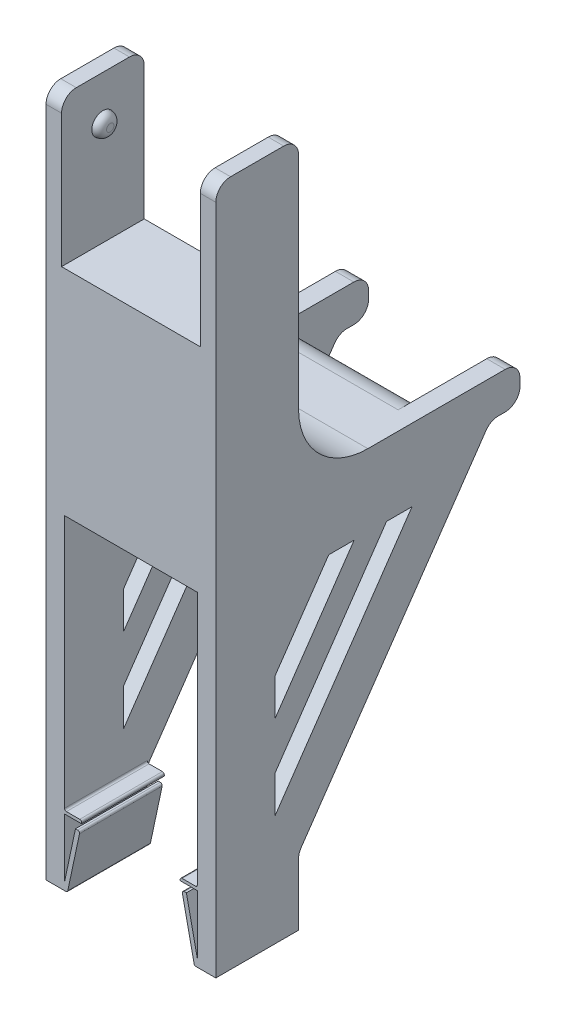
SolidWorks part; units mm, degrees
ref_plane "Front Plane" through (0, 0, 0) normal (0, 0, 1) x (1, 0, 0)
ref_plane "Top Plane" through (0, 0, 0) normal (0, 1, 0) x (1, 0, 0)
ref_plane "Right Plane" through (0, 0, 0) normal (1, 0, 0) x (0, 0, -1)
sketch "Szkic1" plane through (0, 0, 0) normal (1, 0, 0) x (0, 0, -1)
  line L2 (0, 0) -> (-10.3, 0)
  line L5 (-15, 4.7) -> (-15, 20.6)
  line L6 (-15, 20.6) -> (-20.6, 20.6)
  line L7 (-20.6, 20.6) -> (-20.6, -21.4)
  line L8 (0, 0) -> (0, -2.5)
  line L9 (0, -2.5) -> (-2, -2.5)
  line L10 (-2, -2.5) -> (-15, -21.4)
  line L11 (-15, -21.4) -> (-15, -25.9)
  line L12 (-15, -25.9) -> (-20.6, -25.9)
  line L13 (-20.6, -25.9) -> (-20.6, -21.4)
  arc A0 (-15, 4.7) -> (-10.3, 0) centre (-10.3, 4.7) ccw
  point P15 (-10.3, 4.7)
  dimension "D5" = 2.5
  dimension "D7" = 4.7
  dimension "D1" = 42
  dimension "D2" = 20.6
  dimension "D3" = 15.9
  dimension "D4" = 5.6
  dimension "D6" = 2
  dimension "D8" = 18.9
  dimension "D9" = 4.5
extrude "Dodanie-wyciągnięcie1" add sketch "Szkic1" along normal blind 11.5
ref_plane "Płaszczyzna dolna" through (0, 0, 20.6) normal (0, 0, 1) x (1, 0, 0)
sketch "Szkic2" plane through (0, 0, 20.6) normal (0, 0, 1) x (1, 0, 0)
  line L0 (5.75, 20.6) -> (5.75, -25.9) construction
  line L1 (11.5, 20.6) -> (0, 20.6) construction
  line L2 (11.5, -25.9) -> (0, -25.9) construction
  line L4 (10.45, 10.6) -> (1.05, 10.6)
  line L5 (10.45, 10.6) -> (10.45, 20.6)
  line L6 (10.45, 20.6) -> (1.05, 20.6)
  line L7 (1.05, 10.6) -> (1.05, 20.6)
  line L8 (10.45, 10.6) -> (1.05, 20.6) construction
  line L9 (10.45, 20.6) -> (1.05, 10.6) construction
  line L10 (10.25, -3.9) -> (1.25, -3.9)
  line L11 (10.25, -3.9) -> (10.25, -25.9)
  line L12 (10.25, -25.9) -> (1.25, -25.9)
  line L13 (1.25, -3.9) -> (1.25, -25.9)
  line L14 (10.25, -3.9) -> (1.25, -25.9) construction
  line L15 (10.25, -25.9) -> (1.25, -3.9) construction
  point P6 (5.75, 15.6)
  point P11 (5.75, -14.9)
  dimension "D1" = 9.4
  dimension "D2" = 10
  dimension "D3" = 9
  dimension "D4" = 22
extrude "Wytnij-wyciągnięcie1" cut sketch "Szkic2" against normal through all
ref_plane "Płaszczyzna boczna" through (11.5, 0, 0) normal (1, 0, 0) x (0, 0, -1)
sketch "Szkic3" plane through (11.5, 0, 0) normal (1, 0, 0) x (0, 0, -1)
  line L0 (-16.6, -12.7056) -> (-16.6, -10.1985)
  line L1 (-16.6, -10.1985) -> (-12.9555, -4.9)
  line L2 (-12.9555, -4.9) -> (-11.2311, -4.9)
  line L3 (-11.2311, -4.9) -> (-16.6, -12.7056)
  line L4 (-16.6, -15.8972) -> (-16.6, -18.4043)
  line L5 (-16.6, -18.4043) -> (-7.3113, -4.9)
  line L6 (-7.3113, -4.9) -> (-9.0358, -4.9)
  line L7 (-9.0358, -4.9) -> (-16.6, -15.8972)
  line L8 (-15, -21.4) -> (-2, -2.5) construction
  line L10 (-20.6, 6.325) -> (-20.6, -6.325) construction
  line L11 (-20.6, -25.9) -> (-15, -25.9) construction
  point P10 (-13.5626, -3.4254)
  dimension "D1" = 4
  dimension "D2" = 21
extrude "Wytnij-wyciągnięcie2" cut sketch "Szkic3" against normal through all both and the other way through all
ref_plane "Płaszczyzna3" through (0, 0, 0) normal (0, 1, 0) x (1, 0, 0)
sketch "Szkic4" plane through (0, 0, 0) normal (0, 1, 0) x (1, 0, 0)
  line L0 (5.75, -5) -> (5.75, 0) construction
  line L2 (11.5, 0) -> (0, 0) construction
  line L4 (1.25, -5) -> (10.25, -5)
  line L5 (1.25, -5) -> (1.25, 0)
  line L6 (1.25, 0) -> (10.25, 0)
  line L7 (10.25, -5) -> (10.25, 0)
  line L8 (1.25, -5) -> (10.25, 0) construction
  line L9 (1.25, 0) -> (10.25, -5) construction
  point P2 (10.3456, -4.4917)
  point P6 (5.75, -2.5)
  dimension "D1" = 9
  dimension "D2" = 5
extrude "Wytnij-wyciągnięcie3" cut sketch "Szkic4" against normal blind 10
fillet "Zaokrąglenie1" radius 2 2 edges at (5.75, -3.9, 5) (5.75, 0, 5)
fillet "Zaokrąglenie2" radius 1 12 edges at (0.625, 0, 0) (0.625, -2.5, 0) (10.875, -2.5, 0) (10.875, 0, 0) (10.975, 20.6, 20.6) (10.975, 20.6, 15) (0.525, 20.6, 20.6) (0.525, 20.6, 15) (0.625, -2.5, 2) (10.875, -2.5, 2) (0.625, -21.4, 15) (10.875, -21.4, 15)
ref_plane "Płaszczyzna4" through (10.45, 0, 0) normal (-1, 0, 0) x (0, 0, 1)
sketch "Szkic5" plane through (10.45, 0, 0) normal (-1, 0, 0) x (0, 0, 1)
  line L3 (17.8, 20.6) -> (17.8, 10.6) construction
  line L4 (16, 20.6) -> (19.6, 20.6) construction
  line L5 (15, 10.6) -> (20.6, 10.6) construction
  circle A0 centre (17.8, 17.6) radius 0.75
  dimension "D1" = 1.5
  dimension "D2" = 3
extrude "Dodanie-wyciągnięcie2" add sketch "Szkic5" along normal blind 0.5
fillet "Zaokrąglenie3" radius 0.5 1 edges at (9.95, 16.85, 17.8)
ref_plane "Płaszczyzna5" through (5.75, 0, 0) normal (1, 0, 0) x (0, 0, -1)
sketch "Szkic6" plane through (0, 0, 20.6) normal (0, 0, 1) x (1, 0, 0)
  line L0 (10.25, -25.9) -> (10.05, -25.9)
  line L1 (10.05, -25.9) -> (9.1998, -21.9)
  line L2 (9.1998, -21.9) -> (9.5061, -21.9)
  line L4 (10.25, -25.9) -> (10.25, -3.9) construction
  line L5 (10.25, -25.9) -> (10.25, -25.4)
  line L6 (10.25, -25.4) -> (9.5061, -21.9)
  line L7 (10.25, -21.4) -> (9.0885, -21.4)
  line L8 (9.0885, -21.4) -> (9.0885, -21.2)
  line L9 (9.0885, -21.2) -> (10.25, -21.2)
  line L10 (10.25, -21.4) -> (10.25, -21.2)
  dimension "D1" = 4
  dimension "D2" = 0.2
  dimension "D3" = 12
  dimension "D4" = 0.5
  dimension "D5" = 0.5
  dimension "D6" = 0.2
extrude "Dodanie-wyciągnięcie3" add sketch "Szkic6" against normal blind 5.6
fillet "Zaokrąglenie4" radius 0.13 2 edges at (9.1998, -21.9, 17.8) (10.05, -25.9, 17.8)
fillet "Zaokrąglenie5" radius 0.13 2 edges at (10.25, -21.2, 17.8) (9.0885, -21.2, 17.8)
mirror "Lustro2" about plane through (5.75, 0, 0) normal (1, 0, 0) of bodies 115
